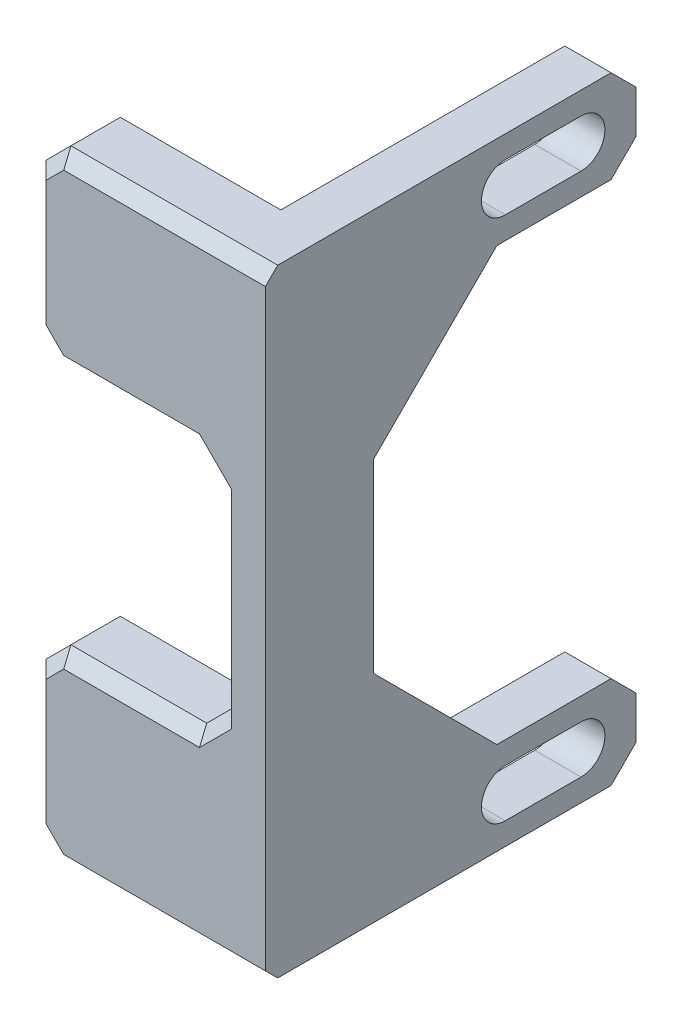
SolidWorks part; units mm, degrees
material "PET"
ref_plane "Front Plane" through (0, 0, 0) normal (0, 0, 1) x (1, 0, 0)
ref_plane "Top Plane" through (0, 0, 0) normal (0, 1, 0) x (1, 0, 0)
ref_plane "Right Plane" through (0, 0, 0) normal (1, 0, 0) x (0, 0, -1)
sketch "Sketch1" plane through (0, 0, 0) normal (1, 0, 0) x (0, 0, -1)
  line L1 (3.175, -31.75) -> (-3.175, -31.75)
  line L2 (3.175, -31.75) -> (3.175, 31.75)
  line L3 (3.175, 31.75) -> (-3.175, 31.75)
  line L4 (-3.175, -31.75) -> (-3.175, 31.75)
  line L5 (3.175, -31.75) -> (-3.175, 31.75) construction
  line L6 (3.175, 31.75) -> (-3.175, -31.75) construction
  point P0 (0, 0)
  dimension "D1" = 63.5
  dimension "D2" = 6.35
extrude "Boss-Extrude1" add sketch "Sketch1" against normal blind 19.05
sketch "Sketch2" plane through (0, 0, 0) normal (1, 0, 0) x (0, 0, -1)
  line L0 (34.925, 0) -> (-3.175, 0) construction
  line L1 (-3.175, 31.75) -> (34.925, 31.75)
  line L2 (-3.175, 31.75) -> (-3.175, -31.75)
  line L3 (-3.175, -31.75) -> (34.925, -31.75)
  line L4 (34.925, 31.75) -> (34.925, 22.225)
  line L5 (3.175, -31.75) -> (3.175, 31.75) construction
  line L6 (34.925, 22.225) -> (7.9375, 22.225)
  line L9 (7.9375, 22.225) -> (7.9375, -22.225)
  line L10 (34.925, -22.225) -> (7.9375, -22.225)
  line L11 (34.925, -22.225) -> (34.925, -31.75)
  point P14 (7.9375, 0)
  dimension "D1" = 38.1
  dimension "D2" = 4.7625
  dimension "D3" = 9.525
extrude "Boss-Extrude2" add sketch "Sketch2" along normal blind 4.7625
sketch "Sketch4" plane through (0, 0, 3.175) normal (0, 0, 1) x (1, 0, 0)
  line L1 (0, -12.7) -> (-19.05, -12.7)
  line L2 (0, -12.7) -> (0, 12.7)
  line L3 (0, 12.7) -> (-19.05, 12.7)
  line L4 (-19.05, -12.7) -> (-19.05, 12.7)
  line L5 (0, -12.7) -> (-19.05, 12.7) construction
  line L6 (0, 12.7) -> (-19.05, -12.7) construction
  line L7 (-19.05, 31.75) -> (-19.05, -31.75) construction
  line L8 (-19.05, 31.75) -> (4.7625, 31.75) construction
  line L9 (0, -31.75) -> (0, 31.75) construction
  point P0 (-9.525, 0)
  dimension "D1" = 19.05
extrude "Cut-Extrude1" cut sketch "Sketch4" against normal up to vertex (6.35 mm away) up to point (0, -31.75, -3.175)
chamfer "Chamfer1" distance 12.7 angle 45 2 edges at (2.3813, -22.225, -7.9375) (2.3813, 22.225, -7.9375)
chamfer "Chamfer2" distance 2.54 angle 45 10 edges at (2.3813, -31.75, -34.925) (2.3813, -22.225, -34.925) (2.3813, 22.225, -34.925) (2.3813, 31.75, -34.925) (-19.05, -31.75, 0) (-19.05, 31.75, 0) (0, 12.7, 0) (0, -12.7, 0) (-19.05, -12.7, 0) (-19.05, 12.7, 0)
chamfer "Chamfer3" distance 1.27 angle 45 13 edges at (-5.8738, -31.75, 3.175) (-17.78, -30.48, 3.175) (-19.05, -22.225, 3.175) (-17.78, -13.97, 3.175) (-9.525, -12.7, 3.175) (-1.27, -11.43, 3.175) (0, 0, 3.175) (-1.27, 11.43, 3.175) (-9.525, 12.7, 3.175) (-17.78, 13.97, 3.175) (-19.05, 22.225, 3.175) (-17.78, 30.48, 3.175) (-5.8738, 31.75, 3.175)
hole_wizard "#8 Clearance Slot1" positions "Sketch6" profile "Sketch7" size "#8" standard "ANSI Inch" slot yes end condition through all
sketch "Sketch6" plane through (4.7625, 0, 0) normal (1, 0, 0) x (0, 0, -1)
  line L0 (34.925, 26.9875) -> (-3.175, 26.9875) construction
  line L1 (34.925, 24.765) -> (34.925, 29.21) construction
  line L2 (-3.175, 30.48) -> (-3.175, -30.48) construction
  line L3 (31.75, 26.9875) -> (19.05, 26.9875) construction
  line L4 (7.9375, 0) -> (-3.175, 0) construction
  line L5 (7.9375, -9.525) -> (7.9375, 9.525) construction
  point P8 (25.4, 26.9875)
  point P20 (25.4, -26.9875)
  dimension "D1" = 12.7
  dimension "D2" = 9.525
sketch "Sketch7" plane through (4.7625, -26.9875, -25.4) normal (0, 1, 0) x (0, 0, -1)
  line L0 (0, 0) -> (0, 23.8125)
  line L1 (0, 23.8125) -> (2.4574, 23.8125)
  line L2 (2.4574, 23.8125) -> (2.4574, 0)
  line L5 (2.4574, 0) -> (0, 0)
  line L11 (0, -6.35) -> (0, 107.95) construction
  dimension "Thru Hole Dia." = 4.9149
  dimension "Thru Hole Depth" = 23.8125
